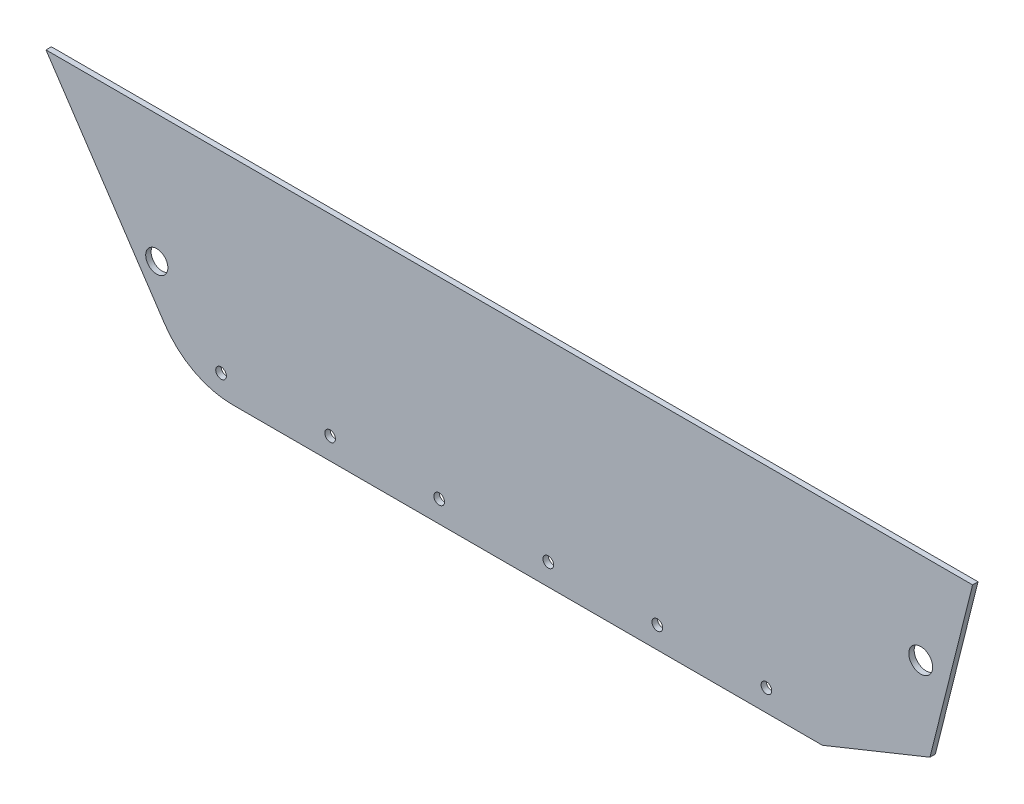
SolidWorks part; units mm, degrees
material "5052-H34"
ref_plane "Front Plane" through (0, 0, 0) normal (0, 0, 1) x (1, 0, 0)
ref_plane "Top Plane" through (0, 0, 0) normal (0, 1, 0) x (1, 0, 0)
ref_plane "Right Plane" through (0, 0, 0) normal (1, 0, 0) x (0, 0, -1)
sketch "Sketch1" plane through (0, 0, 0) normal (0, 0, 1) x (1, 0, 0)
  line L6 (-98.8794, 3.851) -> (-31.8794, -96.649)
  line L7 (428.1206, 28.9396) -> (403.1206, -71.149)
  line L9 (403.1206, -71.149) -> (366, -96.649)
  line L10 (-31.8794, -96.649) -> (366, -96.649)
  line L12 (-98.8794, 3.851) -> (-115.6052, 28.9396)
  line L13 (-115.6052, 28.9396) -> (428.1206, 28.9396)
  circle A0 centre (-12.8794, -83.899) radius 3.125
  circle A1 centre (51.1206, -83.899) radius 3.125
  circle A2 centre (115.1206, -83.899) radius 3.125
  circle A3 centre (179.1206, -83.899) radius 3.125
  circle A4 centre (243.1206, -83.899) radius 3.125
  circle A5 centre (307.1206, -83.899) radius 3.125
  point P0 (-48.8794, -71.149)
  point P2 (-31.8794, -96.649)
  point P8 (48, -83.899)
  point P9 (403.1206, -71.149)
  dimension "D2" = 64
  dimension "D4" = 64
  dimension "D15" = 6.25
  dimension "D1" = 25.5
  dimension "D3" = 75
  dimension "D5" = 25
  dimension "D6" = 96
  dimension "D7" = 527
  dimension "D8" = 180
  dimension "D9" = 64
  dimension "D10" = 64
  dimension "D11" = 64
  dimension "D12" = 123.69
  dimension "D13" = 12.75
  dimension "D14" = 543.7258
  dimension "D16" = 366
extrude "Boss-Extrude1" add sketch "Sketch1" along normal blind 3.175 contours L12 L13 L7 L9 L10 L6
extrude "Cut-Extrude1" cut sketch "Sketch1<4>" along normal through all contours A0 | A1 | A2 | A3 | A4 | A5 region at (-12.8794, -83.899, 0)
sketch "Sketch1<4>" plane through (0, 0, 0) normal (0, 0, 1) x (1, 0, 0) same geometry as "Sketch1"
sketch "Sketch2" plane through (0, 0, 0) normal (0, 0, -1) x (-1, 0, 0)
  circle A0 centre (-275.1206, -83.899) radius 6.5
  circle A2 centre (-233.5603, -132.5687) radius 6.5
  circle A3 centre (-192, -83.899) radius 6.5
  circle A4 centre (-128, -83.899) radius 6.5
  circle A5 centre (-64, -83.899) radius 6.5
  circle A6 centre (0, -83.899) radius 6.5
  dimension "D2" = 0
  dimension "D3" = 64
  dimension "D4" = 64
  dimension "D5" = 64
  dimension "D6" = 64
  dimension "D7" = 64
  dimension "D1" = 32
sketch "Sketch5" plane through (0, 0, 0) normal (0, 0, -1) x (-1, 0, 0)
  line L0 (48.8794, -71.149) -> (-14.2353, -96.649)
  line L1 (31.8794, -96.649) -> (-366, -96.649) construction
  line L2 (-14.2353, -96.649) -> (31.8794, -96.649)
  line L3 (31.8794, -96.649) -> (48.8794, -71.149)
  line L6 (-366, -96.649) -> (-403.1206, -71.149)
  line L7 (-403.1206, -71.149) -> (-352, -71.149)
  line L9 (-352, -71.149) -> (-326.5, -96.649)
  line L11 (-366, -96.649) -> (-326.5, -96.649)
  dimension "D1" = 22
  dimension "D2" = 45
extrude "Cut-Extrude2" [suppressed] cut sketch "Sketch5" against normal up to next
sketch "Sketch6" plane through (0, 0, 3.175) normal (0, 0, 1) x (1, 0, 0)
  line L0 (-48.8794, -71.149) -> (14.2353, -96.649)
  line L1 (-31.8794, -96.649) -> (366, -96.649) construction
  line L2 (14.2353, -96.649) -> (-31.8794, -96.649)
  line L3 (-31.8794, -96.649) -> (-48.8794, -71.149)
  dimension "D1" = 158
fillet "Fillet1" radius 48 1 edges at (-31.8794, -96.649, 1.5875)
sketch "Sketch7" plane through (0, 0, 3.175) normal (0, 0, 1) x (1, 0, 0)
  line L0 (403.1206, -71.149) -> (340.0059, -96.649)
  line L1 (-31.8794, -96.649) -> (366, -96.649) construction
  line L2 (340.0059, -96.649) -> (366, -96.649)
  line L3 (366, -96.649) -> (403.1206, -71.149)
  dimension "D1" = 22
extrude "Cut-Extrude3" cut sketch "Sketch7" against normal blind 10
sketch "Sketch9" plane through (0, 0, 0) normal (0, 0, -1) x (-1, 0, 0)
  line L0 (-403.1206, -71.149) -> (48.8794, -71.149)
  line L1 (48.8794, -71.149) -> (48.8794, -114.9143)
  line L2 (48.8794, -114.9143) -> (-403.1206, -114.9143)
  line L3 (-403.1206, -114.9143) -> (-403.1206, -71.149)
extrude "Cut-Extrude4" [suppressed] cut sketch "Sketch9" against normal blind 10
sketch "Sketch12" plane through (0, 0, 3.175) normal (0, 0, 1) x (1, 0, 0)
  circle A0 centre (397.6778, -24.6104) radius 7
  dimension "D1" = 14
extrude "Cut-Extrude5" cut sketch "Sketch12" against normal up to next
sketch "Sketch13" plane through (0, 0, 3.175) normal (0, 0, 1) x (1, 0, 0)
  line L2 (397.6778, -24.6104) -> (397.6778, -124.8724) construction
  line L3 (-115.6052, 28.9396) -> (428.1206, 28.9396) construction
  circle A0 centre (-50.6052, -46.0604) radius 6.5
  dimension "D2" = 13
  dimension "D1" = 65
  dimension "D3" = 75
extrude "Cut-Extrude6" cut sketch "Sketch13" against normal blind 10
